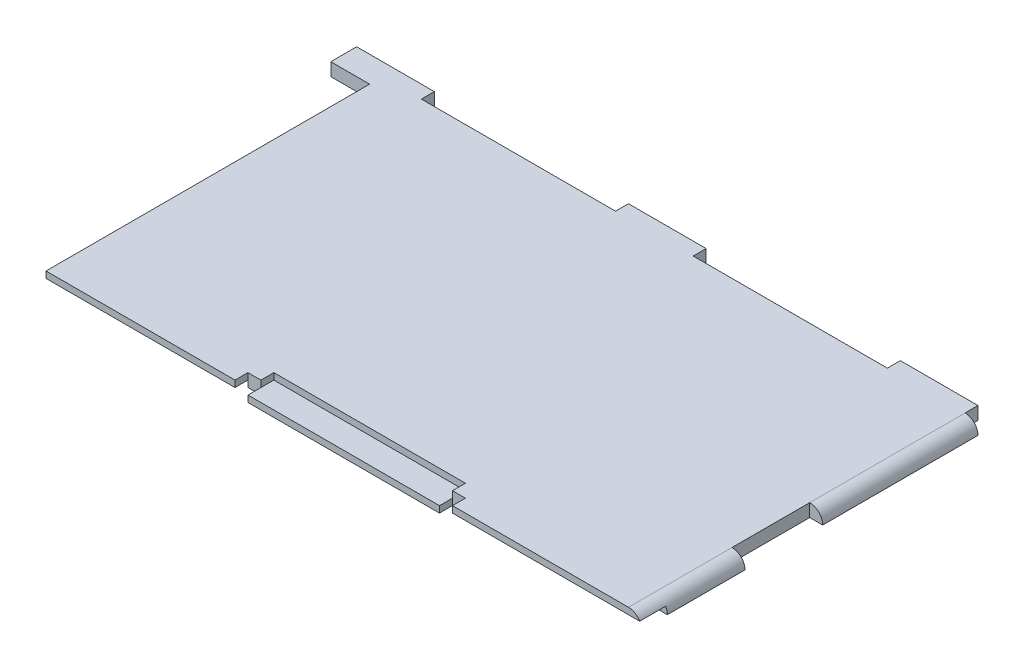
SolidWorks part; units mm, degrees
ref_plane "前基準面" through (0, 0, 0) normal (0, 0, 1) x (1, 0, 0)
ref_plane "上基準面" through (0, 0, 0) normal (0, 1, 0) x (1, 0, 0)
ref_plane "右基準面" through (0, 0, 0) normal (1, 0, 0) x (0, 0, -1)
sketch "草圖1" plane through (0, 0, 0) normal (0, 1, 0) x (1, 0, 0)
  line L0 (-36.2537, 43.5351) -> (203.7463, 43.5351)
  line L1 (203.7463, 43.5351) -> (203.7463, -286.4649)
  line L2 (198.7463, -286.4649) -> (198.7463, -256.4649)
  line L3 (198.7463, -256.4649) -> (183.2463, -256.4649)
  line L4 (183.2463, -256.4649) -> (183.2463, -266.4649)
  line L5 (183.2463, -266.4649) -> (124.7463, -266.4649)
  line L6 (124.7463, -266.4649) -> (124.7463, -262.4649)
  line L7 (124.7463, -262.4649) -> (109.2463, -262.4649)
  line L8 (109.2463, -262.4649) -> (109.2463, -266.4649)
  line L9 (109.2463, -266.4649) -> (-21.2537, -266.4649)
  line L10 (-21.2537, -266.4649) -> (-21.2537, 38.5351)
  line L11 (-21.2537, 38.5351) -> (-36.2537, 38.5351)
  line L12 (-36.2537, 38.5351) -> (-36.2537, 43.5351)
  line L13 (198.7463, -286.4649) -> (203.7463, -286.4649)
  line L15 (203.7463, -286.4649) -> (208.7463, -286.4649)
  line L16 (203.7463, -286.4649) -> (203.7463, -226.4649)
  line L17 (203.7463, -226.4649) -> (208.7463, -226.4649)
  line L18 (208.7463, -286.4649) -> (208.7463, -226.4649)
  line L19 (-36.2537, 43.5351) -> (-6.2537, 43.5351)
  line L20 (-36.2537, 43.5351) -> (-36.2537, 48.5351)
  line L21 (-36.2537, 48.5351) -> (-6.2537, 48.5351)
  line L22 (-6.2537, 43.5351) -> (-6.2537, 48.5351)
  line L23 (203.7463, 43.5351) -> (173.7463, 43.5351)
  line L24 (203.7463, 43.5351) -> (203.7463, 48.5351)
  line L25 (203.7463, 48.5351) -> (173.7463, 48.5351)
  line L26 (173.7463, 43.5351) -> (173.7463, 48.5351)
  line L27 (203.7463, 43.5351) -> (208.7463, 43.5351)
  line L28 (203.7463, 43.5351) -> (203.7463, -16.4649)
  line L29 (203.7463, -16.4649) -> (208.7463, -16.4649)
  line L30 (208.7463, 43.5351) -> (208.7463, -16.4649)
  line L31 (83.7463, 43.5351) -> (98.7463, 43.5351)
  line L32 (83.7463, 43.5351) -> (83.7463, 48.5351)
  line L33 (83.7463, 48.5351) -> (98.7463, 48.5351)
  line L34 (98.7463, 43.5351) -> (98.7463, 48.5351)
  line L35 (83.7463, 43.5351) -> (68.7463, 43.5351)
  line L36 (83.7463, 43.5351) -> (83.7463, 48.5351)
  line L37 (83.7463, 48.5351) -> (68.7463, 48.5351)
  line L38 (68.7463, 43.5351) -> (68.7463, 48.5351)
  line L39 (203.7463, -46.4649) -> (208.7463, -46.4649)
  line L40 (203.7463, -46.4649) -> (203.7463, -106.4649)
  line L41 (203.7463, -106.4649) -> (208.7463, -106.4649)
  line L42 (208.7463, -46.4649) -> (208.7463, -106.4649)
  line L43 (203.7463, -136.4649) -> (208.7463, -136.4649)
  line L44 (203.7463, -136.4649) -> (203.7463, -196.4649)
  line L45 (203.7463, -196.4649) -> (208.7463, -196.4649)
  line L46 (208.7463, -136.4649) -> (208.7463, -196.4649)
  dimension "D3" = 5
  dimension "D1" = 240
  dimension "D2" = 330
  dimension "D4" = 15
  dimension "D5" = 130.5
  dimension "D6" = 4
  dimension "D7" = 4
  dimension "D8" = 15.5
  dimension "D9" = 58.5
  dimension "D10" = 10
  dimension "D11" = 15.5
  dimension "D12" = 30
  dimension "D13" = 5
  dimension "D14" = 60
  dimension "D15" = 5
  dimension "D16" = 5
  dimension "D17" = 30
  dimension "D18" = 5
  dimension "D19" = 30
  dimension "D20" = 60
  dimension "D21" = 5
  dimension "D22" = 5
  dimension "D23" = 15
  dimension "D24" = 5
  dimension "D25" = 15
  dimension "D26" = 60
  dimension "D27" = 5
  dimension "D28" = 30
  dimension "D29" = 60
  dimension "D30" = 5
  dimension "D31" = 30
  dimension "D32" = 30
extrude "填料-伸長1" add sketch "草圖1" along normal blind 5 contours L2 L13 L1 L0 L12 L11 L10 L9 L8 L7 L6 L5 L4 L3 | L15 L18 L17 L1 | L30 L27 L1 L29 | L26 L0 L24 L25 | L0 L22 L21 L20 | L32 L33 L34 L31 | L36 L37 L38 L35 | L46 L45 L44 L43 | L42 L41 L40 L39 region at (-21.2537, 0, -46.0351) region at (91.0303, 0, 111.0679) region at (188.7463, 0, -46.0351) region at (206.2463, 0, -13.5351) region at (206.2463, 0, 256.4649)
fillet "圓角1" radius 5 4 edges at (208.7463, 5, -13.5351) (208.7463, 5, 76.4649) (208.7463, 5, 166.4649) (208.7463, 5, 256.4649)
sketch "草圖2" plane through (0, 5, 0) normal (0, 1, 0) x (1, 0, 0)
  line L0 (208.7463, -136.4649) -> (203.7463, -136.4649) construction
  line L1 (208.7463, -86.4649) -> (-30.7437, -86.4649)
  line L2 (208.7463, -86.4649) -> (208.7463, -299.5734)
  line L3 (208.7463, -299.5734) -> (-30.7437, -299.5734)
  line L4 (-30.7437, -86.4649) -> (-30.7437, -299.5734)
  dimension "D1" = 50
extrude "除料-伸長2" cut sketch "草圖2" against normal blind 10
sketch "草圖3" plane through (0, 0, 86.4649) normal (0, 0, 1) x (1, 0, 0)
  line L0 (208.7463, 0) -> (-21.2537, 0) construction
  line L1 (-21.2537, 0) -> (51.7463, 0)
  line L2 (-21.2537, 0) -> (-21.2537, 2.5)
  line L3 (-21.2537, 2.5) -> (51.7463, 2.5)
  line L4 (51.7463, 0) -> (51.7463, 2.5)
  line L6 (135.7463, 2.5) -> (208.7463, 2.5)
  line L7 (135.7463, 2.5) -> (135.7463, 0)
  line L8 (135.7463, 0) -> (208.7463, 0)
  line L9 (208.7463, 2.5) -> (208.7463, 0)
  line L10 (56.7463, 2.5) -> (130.7463, 2.5)
  line L11 (56.7463, 2.5) -> (56.7463, 5)
  line L12 (56.7463, 5) -> (130.7463, 5)
  line L13 (130.7463, 2.5) -> (130.7463, 5)
  line L14 (203.7463, 5) -> (-21.2537, 5) construction
  point P4 (0, 0)
  dimension "D1" = 2.5
  dimension "D2" = 73
  dimension "D3" = 73
  dimension "D4" = 2.5
  dimension "D5" = 2.5
  dimension "D6" = 5
  dimension "D7" = 5
  dimension "D8" = 74
  dimension "D9" = 0
  dimension "D10" = 2.5
  dimension "D11" = 0
extrude "除料-伸長3" cut sketch "草圖3" against normal blind 10
sketch "草圖4" plane through (0, 0, 86.4649) normal (0, 0, 1) x (1, 0, 0)
  line L0 (135.7463, 2.5) -> (135.7463, 0) construction
  line L5 (51.7463, 0) -> (56.7463, 0)
  line L6 (51.7463, 0) -> (51.7463, 5)
  line L7 (51.7463, 5) -> (56.7463, 5)
  line L8 (56.7463, 0) -> (56.7463, 5)
  line L9 (130.7463, 5) -> (135.7463, 5)
  line L10 (130.7463, 5) -> (130.7463, 0)
  line L11 (130.7463, 0) -> (135.7463, 0)
  line L12 (135.7463, 5) -> (135.7463, 0)
  line L13 (135.7463, 0) -> (51.7463, 0) construction
extrude "除料-伸長4" cut sketch "草圖4" against normal blind 5
